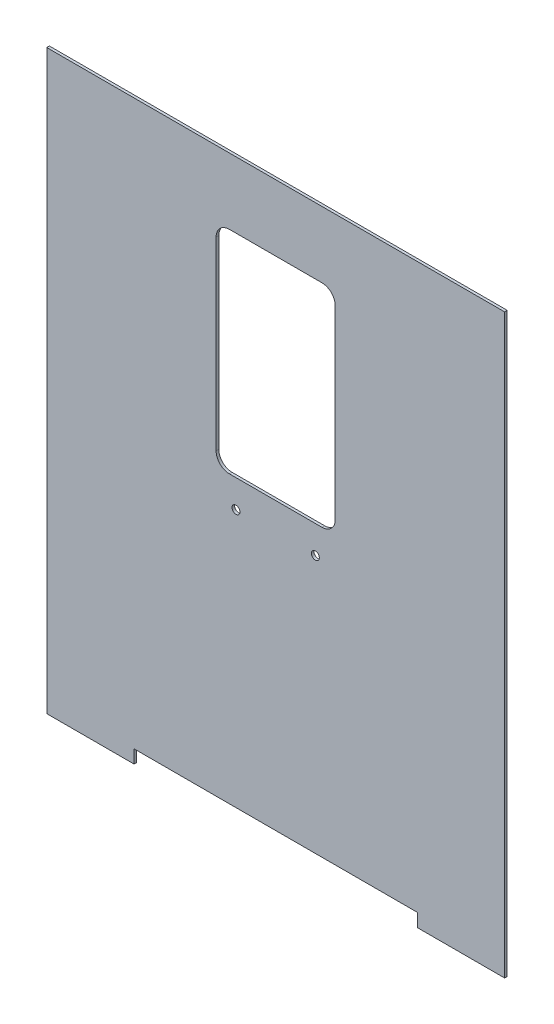
SolidWorks part; units mm, degrees
note: The reader was unsure of these and kept them because the rebuilt part matched: thickness of "Tôle de base pliée1", "Tôlerie1", "Tôlerie2".
material "Film PE haute densité"
ref_plane "Plan de face" through (0, 0, 0) normal (0, 0, 1) x (1, 0, 0)
ref_plane "Plan de dessus" through (0, 0, 0) normal (0, 1, 0) x (1, 0, 0)
ref_plane "Plan de droite" through (0, 0, 0) normal (1, 0, 0) x (0, 0, -1)
sketch "Esquisse1" plane through (0, 0, 0) normal (0, 0, 1) x (1, 0, 0)
  line L0 (53.5, 0) -> (86.5, 0)
  line L1 (-86.5, 218) -> (86.5, 218)
  line L2 (-86.5, 218) -> (-86.5, 0)
  line L3 (-86.5, 0) -> (-53.5, 0)
  line L4 (86.5, 218) -> (86.5, 0)
  line L5 (-53.5, 0) -> (53.5, 0) construction
  line L6 (-53.5, 0) -> (-53.5, 5)
  line L7 (-53.5, 5) -> (53.5, 5)
  line L8 (53.5, 0) -> (53.5, 5)
  dimension "D1" = 218
  dimension "D2" = 173
  dimension "D3" = 107
  dimension "D4" = 5
base flange "Tôle de base pliée1" sketch "Esquisse1" thickness 1 reverse thickness direction no parameters "D1"=1
sketch "Esquisse2" plane through (0, 0, 0) normal (0, 0, 1) x (1, 0, 0)
  line L0 (0, 0) -> (0, 113) construction
  line L1 (-53.5, 5) -> (53.5, 5) construction
  line L2 (-22.5, 193) -> (22.5, 193)
  line L3 (-22.5, 193) -> (-22.5, 113)
  line L4 (-22.5, 113) -> (22.5, 113)
  line L5 (22.5, 193) -> (22.5, 113)
  line L6 (86.5, 218) -> (-86.5, 218) construction
  circle A0 centre (-15, 102.5) radius 1.5
  circle A1 centre (15, 102.5) radius 1.5
  dimension "D1" = 3
  dimension "D2" = 97.5
  dimension "D6" = 30
  dimension "D3" = 10.5
  dimension "D4" = 25
  dimension "D5" = 45
  dimension "D7" = 80
extrude "Enlèv. mat.-Extru.1" cut sketch "Esquisse2" against normal blind 1 normal cut yes
fillet "Congé1" radius 5 4 edges at (22.5, 193, -0.5) (22.5, 113, -0.5) (-22.5, 113, -0.5) (-22.5, 193, -0.5)
sketch "Lignes de pliage1" [suppressed] plane through (0, 0, 0) normal (0, 1, 0) x (1, 0, 0)
sketch "Cube de visualisation1" [suppressed] plane through (0, 0, 0) normal (0, 1, 0) x (1, 0, 0)
sheet metal parameters "Tôlerie1" thickness 1 parameters "D1"=1, "D7"=2
flat pattern "Etat déplié1" [suppressed]
sketch "Lignes de pliage2" plane through (0, 0, 0) normal (0, 1, 0) x (1, 0, 0)
sketch3d "Cube de visualisation2" [suppressed]
  line L0 (90, 200, 0) -> (90, 0, 0) construction
  line L1 (-90, 200, 0) -> (-90, 0, 0) construction
  line L2 (90, 200, 0) -> (-90, 200, 0) construction
  line L3 (90, 0, 0) -> (-90, 0, 0) construction
sheet metal parameters "Tôlerie2" thickness 1 parameters "D1"=1, "D7"=2
flat pattern "Etat déplié1"
sketch "Lignes de pliage2" plane through (0, 0, 0) normal (0, 1, 0) x (1, 0, 0)
sketch3d "Cube de visualisation2" [suppressed]
  line L0 (86.5, 218, 0) -> (86.5, 0, 0) construction
  line L1 (-86.5, 218, 0) -> (-86.5, 0, 0) construction
  line L2 (86.5, 218, 0) -> (-86.5, 218, 0) construction
  line L3 (86.5, 0, 0) -> (-86.5, 0, 0) construction
